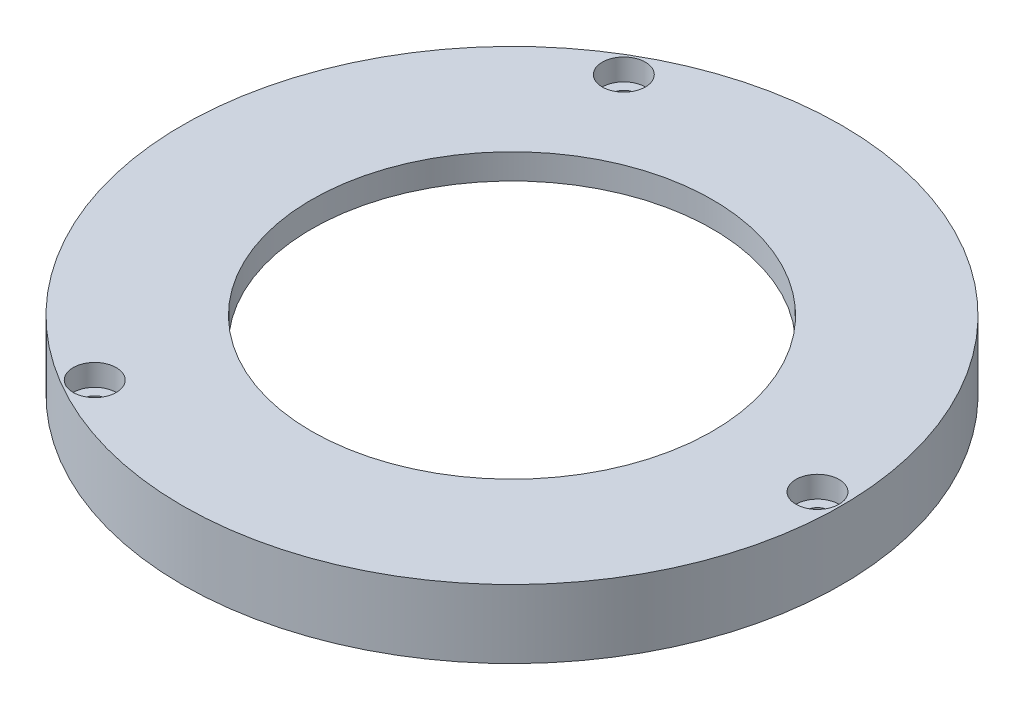
SolidWorks part; units mm, degrees
ref_plane "Front Plane" through (0, 0, 0) normal (0, 0, 1) x (1, 0, 0)
ref_plane "Top Plane" through (0, 0, 0) normal (0, 1, 0) x (1, 0, 0)
ref_plane "Right Plane" through (0, 0, 0) normal (1, 0, 0) x (0, 0, -1)
sketch "Sketch1" plane through (0, 0, 0) normal (0, 1, 0) x (1, 0, 0)
  line L0 (0, 0) -> (42.5, 0) construction
  circle A0 centre (0, 0) radius 45.85
  circle A1 centre (0, 0) radius 27.9
  circle A2 centre (42.5, 0) radius 1.5635
  circle A3 centre (-21.25, -36.8061) radius 1.5635
  circle A4 centre (-21.25, 36.8061) radius 1.5635
  circle A5 centre (0, 0) radius 39.3
  point P13 (0, 0)
  dimension "D1" = 91.7
  dimension "D2" = 55.8
  dimension "D4" = 3.127
  dimension "D6" = 78.6
  dimension "D3" = 42.5
  dimension "D5" = 3
extrude "Boss-Extrude1" add sketch "Sketch1" against normal blind 6 contours A0 A5 A2 A4 A3 region at (-44.5532, 0, 0)
extrude "Boss-Extrude2" add sketch "Sketch1<4>" along normal blind 3.525 contours A1 A5 | A0 A5 A2 A4 A3 region at (-44.5532, 0, 0) region at (-38.1884, 0, 0)
sketch "Sketch1<4>" plane through (0, 0, 0) normal (0, 1, 0) x (1, 0, 0) same geometry as "Sketch1"
sketch "Sketch2" plane through (0, 3.525, 0) normal (0, 1, 0) x (1, 0, 0)
  circle A0 centre (42.5, 0) radius 3
  circle A1 centre (-21.25, -36.8061) radius 3
  circle A2 centre (-21.25, 36.8061) radius 3
  point P9 (0, 0)
  dimension "D1" = 6
  dimension "D2" = 3
extrude "Cut-Extrude1" cut sketch "Sketch2" against normal blind 3
equation "\"bearing_21_OD\"= 21mm"
equation "\"pin_cirlce_diameter\"= 75mm"
equation "\"pin_diam\"= 6mm"
equation "\"gear_thickness\"= 4mm"
equation "\"ball_bearing_diam\"= 3.214mm"
equation "\"bearing_21_outer_clearance\"= 0.127mm'change this"
equation "\"bearing_15_OD\"= 15mm"
equation "\"bearing_15_outer_clearance\"= 0mm'change this"
equation "\"thrust_bearing_thickness\"= 5mm'measure this irl and change"
equation "\"D1@Boss-Extrude1\"=\"thrustBearingThickness\"+1mm"
equation "\"largeBearOD\"= 21mm"
equation "\"largeBearID\" = 15mm"
equation "\"largeBearOTight\"= 0.127mm'calibrate - hold onto gears"
equation "\"largeBearITight\"= 0mm'calibrate - hold onto eccentric nut"
equation "\"largeBearFlangeDiam\" = 22.5mm"
equation "\"largeBearFlangeWidth\" = 0.8mm"
equation "\"smallBearOD\"= 15mm"
equation "\"smallBearOTight\"= 0mm'calibrate - hold onto bottom of gearbox"
equation "\"smallBearOLoose\"= 0mm'calibrate - able to take off topHat"
equation "\"smallBearID\" = 10mm"
equation "\"smallBearITight\" = 0mm'hold onto "
equation "\"pinCircleDiam\"= 75mm"
equation "\"pinDiam\"= 6mm"
equation "\"sheetThickness\"= 0.1875in"
equation "\"ballBearDiam\"= 3.214mm"
equation "\"thrustBearingThickness\"= 5mm'measure this irl and change"
equation "\"thrustBearingID\"= 0mm'measure this irl and change"
equation "\"thrustBearingOD\"= 0mm'measure this irl and change"
equation "\"eccentricity\" = 1mm"
equation "\"D1@Boss-Extrude2\"=\"sheetThickness\"*2-(\"thrustBearingThickness\"+1)"
